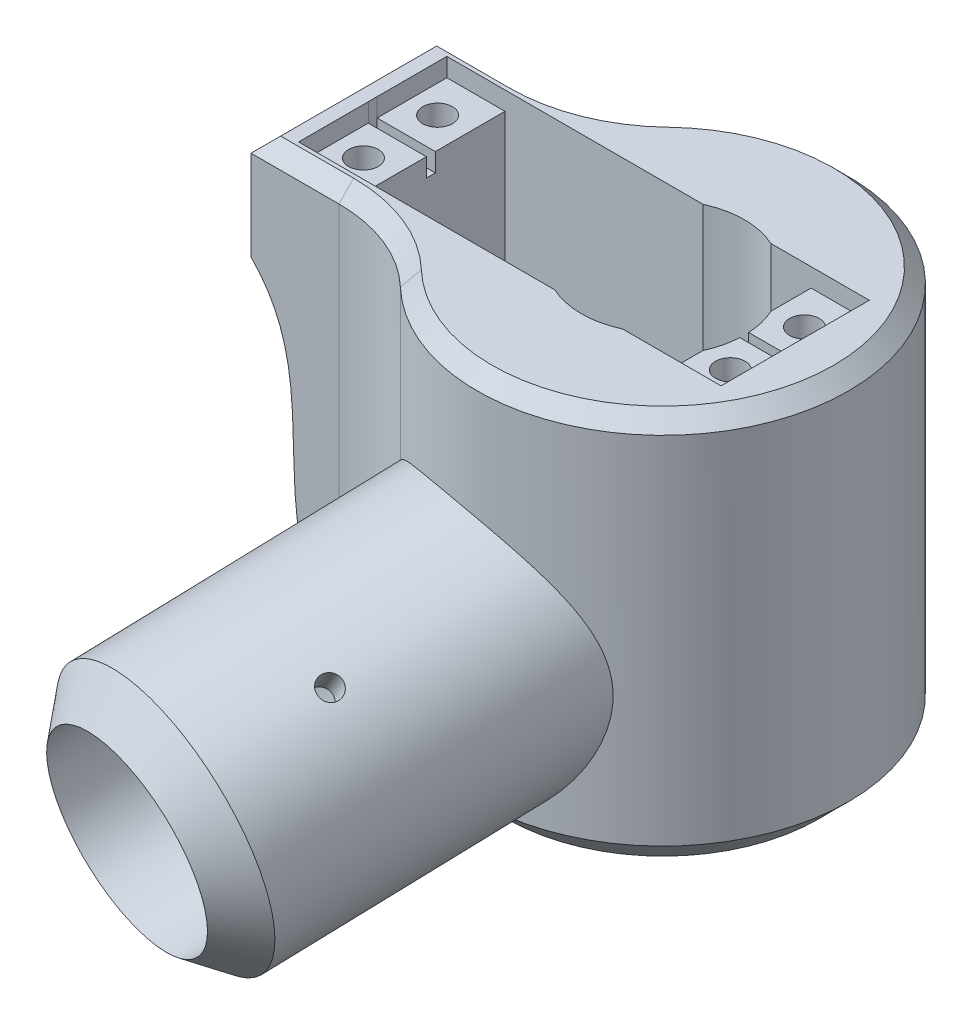
SolidWorks part; units mm, degrees
material "Melamine resin"
ref_plane "Front Plane" through (0, 0, 0) normal (0, 0, 1) x (1, 0, 0)
ref_plane "Top Plane" through (0, 0, 0) normal (0, 1, 0) x (1, 0, 0)
ref_plane "Right Plane" through (0, 0, 0) normal (1, 0, 0) x (0, 0, -1)
sketch "Sketch1" plane through (0, 0, 0) normal (0, 1, 0) x (1, 0, 0)
  line L3 (-34.0477, -12.5248) -> (-22.1886, -12.5248)
  line L4 (-34.0477, -12.5248) -> (-34.0477, 12.5248)
  line L5 (-34.0477, 12.5248) -> (-22.1886, 12.5248)
  arc A3 (-8.3278, -18.0914) -> (-22.1886, -12.5248) centre (-22.1886, -32.5646) ccw
  arc A4 (-22.1886, 12.5248) -> (-8.3278, 18.0914) centre (-22.1886, 32.5646) ccw
  arc A5 (-8.3278, -18.0914) -> (-8.3278, 18.0914) centre (8.9981, 0) ccw
  dimension "D1" = 20.0397
  dimension "D2" = 25.0497
extrude "Boss-Extrude2" add sketch "Sketch1" along normal blind 54
ref_axis "Axis1" through (8.9981, 54, 0) along (0, -1, 0)
ref_point "Point1"
sketch3d "3DSketch1"
  line L0 (8.9981, 25, 0) -> (-7.5398, 5.3755, 91.6321)
  line L4 (-23.4294, -13.4798, 179.6725) -> (8.9981, 25, 0) construction
ref_plane "Plane1" through (0, 25, 0) normal (0, 1, 0) x (1, 0, 0)
sketch "Sketch2" plane through (0, 25, 0) normal (0, 1, 0) x (1, 0, 0)
  point P0 (8.9981, 0)
chamfer "Chamfer1" distance 2 angle 45 5 edges at (-14.7202, 54, 13.9685) (-14.7202, 54, -13.9685) (34.0477, 54, 0) (-28.1181, 54, 12.5248) (-28.1181, 54, -12.5248)
ref_plane "Plane2" through (8.9981, 25, 0) normal (-0.1738, -0.2062, 0.9629) x (0.9848, -0.0364, 0.1699)
sketch "Sketch3" plane through (8.9981, 25, 0) normal (-0.1738, -0.2062, 0.9629) x (0.9848, -0.0364, 0.1699)
  circle A0 centre (0, 0) radius 17.5
  dimension "D1" = 35
extrude "Boss-Extrude3" add sketch "Sketch3" along a picked direction on the side of the normal blind 65
sketch "Sketch5" plane through (-10.1287, -12.0192, 56.1209) normal (-0.1738, -0.2062, 0.9629) x (0.9848, -0.0373, 0.1698)
  circle A0 centre (7.9298, 24.4526) radius 12.9
  dimension "D1" = 25.8
extrude "Cut-Extrude1" cut sketch "Sketch5" against normal blind 40
chamfer "Chamfer2" distance 6 angle 45 1 edges at (-2.2985, -5.5169, 58.9267)
ref_plane "Plane3" through (-22.1886, 52, -12.5248) normal (-0.5664, -0.779, -0.2691) x (-0.8242, 0.5354, 0.1848)
sketch "Sketch6" plane through (-22.1886, 52, -12.5248) normal (-0.5664, -0.779, -0.2691) x (-0.8242, 0.5354, 0.1848)
  line L0 (-26.8776, -71.5719) -> (-28.5511, -63.7489) construction
  line L2 (-37.8434, -20.6484) -> (-17.7885, -113.6691) construction
  circle A0 centre (-28.5511, -63.7489) radius 1.5
  dimension "D1" = 3
  dimension "D2" = 8
extrude "Cut-Extrude2" cut sketch "Sketch6" against normal mid plane 97
ref_point "Point2"
sketch "Sketch7" plane through (0, 0, 0) normal (0, -1, 0) x (-1, 0, 0)
  circle A0 centre (-8.9981, 0) radius 4
  dimension "D1" = 8
extrude "Cut-Extrude3" cut sketch "Sketch7" against normal blind 82
sketch "Sketch9" plane through (0, 0, 0) normal (0, -1, 0) x (1, 0, 0)
  circle A0 centre (8.9981, 0) radius 11
  dimension "D1" = 22
extrude "Cut-Extrude4" cut sketch "Sketch9" against normal blind 8
chamfer "Chamfer3" distance 2 angle 45 1 edges at (-34.0477, 54, 0)
sketch "Sketch10" plane through (0, 0, -12.5248) normal (0, 0, -1) x (-1, 0, 0)
  line L0 (22.1867, 0) -> (34.0477, 0)
  line L1 (34.0477, 0) -> (34.0477, 39.8592)
  line L2 (34.0477, 52) -> (34.0477, 0) construction
  line L3 (34.0477, 52) -> (22.1886, 52) construction
  spline S0 degree 3 poles (22.1867, 0) (33.5541, 11.2638) (23.1647, 28.9343) (34.0477, 39.8592) knots 0 0 0 0 1 1 1 1
extrude "Cut-Extrude5" cut sketch "Sketch10" against normal blind 96
sketch3d "3DSketch2"
  line L0 (8.9981, 54, 0) -> (8.9981, 0, 0) construction
  point P0 (8.9981, 25, 0)
sketch "Sketch11" plane through (0, 54, 0) normal (0, 1, 0) x (1, 0, 0)
  line L0 (25.8463, 0) -> (-43.2495, 0) construction
  line L1 (18.9981, 10.25) -> (-22.3055, 10.25)
  line L2 (18.9981, 10.25) -> (18.9981, -10.25)
  line L3 (18.9981, -10.25) -> (-22.3055, -10.25)
  line L4 (-22.3055, 10.25) -> (-22.3055, -10.25)
  line L5 (18.9981, 10.25) -> (-22.3055, -10.25) construction
  line L6 (18.9981, -10.25) -> (-22.3055, 10.25) construction
  line L7 (-29.1537, 10) -> (25.8463, 10)
  line L8 (-29.1537, 10) -> (-29.1537, -10)
  line L9 (-29.1537, -10) -> (25.8463, -10)
  line L10 (25.8463, 10) -> (25.8463, -10)
  line L11 (-29.1537, 10) -> (25.8463, -10) construction
  line L12 (-29.1537, -10) -> (25.8463, 10) construction
  line L13 (-1.6537, 0) -> (-1.6537, -13.0522) construction
  line L14 (12.1499, 0.6) -> (25.8463, 0.6)
  line L15 (12.1499, 0.6) -> (12.1499, -0.6)
  line L16 (12.1499, -0.6) -> (25.8463, -0.6)
  line L17 (25.8463, 0.6) -> (25.8463, -0.6)
  line L18 (12.1499, 0.6) -> (25.8463, -0.6) construction
  line L19 (12.1499, -0.6) -> (25.8463, 0.6) construction
  line L20 (-1.6537, -13.0522) -> (-1.6537, 13.6107) construction
  line L21 (-29.1537, 10) -> (-29.1537, -10)
  line L22 (-15.4573, 0.6) -> (-15.4573, -0.6)
  line L23 (-15.4573, -0.6) -> (-29.1537, -0.6)
  line L24 (-15.4573, 0.6) -> (-29.1537, 0.6)
  circle A0 centre (23.0963, -5) radius 2
  circle A1 centre (23.0963, 5) radius 2
  circle A2 centre (-26.4037, -5) radius 2
  circle A3 centre (-26.4037, 5) radius 2
  point P0 (7.4947, -4.5406)
  point P5 (-1.6537, 0)
  point P10 (18.9981, 0)
  circle M6 centre (8.9981, 0) radius 4
  dimension "D5" = 4
  dimension "D1" = 20.5
  dimension "D2" = 41.3036
  dimension "D3" = 55
  dimension "D4" = 1.2
  dimension "D6" = 5
  dimension "D7" = 2.75
  dimension "D8" = 10
extrude "Cut-Extrude6" cut sketch "Sketch11" against normal blind 34 contours L24 L22 L23 L4 L9 L2 L16 L14 L7 M6 | A1 | A0 | A2 | A3 | L16 L2 L14 M6 | L15 L16 L14 M6 | L16 L15 L14 M6 | L22 L24 L4 L23 region at (-2.3392, 54, 0) region at (15.9905, 54, 0) region at (-18.8814, 54, 0) region at (12.5665, 54, 0) region at (8.9256, 54, 0) region at (23.0963, 54, 5) region at (23.0963, 54, -5) region at (-26.4037, 54, 5) region at (-26.4037, 54, -5)
sketch "Sketch12" plane through (0, 54, 0) normal (0, 1, 0) x (1, 0, 0)
  line L0 (18.9981, 0) -> (-33.6264, 0) construction
  line L1 (18.9981, 10) -> (18.9981, -10) construction
  line L2 (0, 0) -> (0, -14.2019) construction
  line L3 (11.1481, 0.6) -> (26.8481, 0.6)
  line L4 (11.1481, 0.6) -> (11.1481, -0.6)
  line L5 (11.1481, -0.6) -> (26.8481, -0.6)
  line L6 (26.8481, 0.6) -> (26.8481, -0.6)
  line L7 (11.1481, 0.6) -> (26.8481, -0.6) construction
  line L8 (11.1481, -0.6) -> (26.8481, 0.6) construction
  line L9 (0, -14.2019) -> (0, 17.0976) construction
  line L10 (18.9981, 10) -> (18.9981, -10) construction
  line L11 (-22.3055, 10) -> (-22.3055, -10) construction
  line L12 (-14.4555, 0.6) -> (-30.1555, 0.6)
  line L13 (-14.4555, 0.6) -> (-14.4555, -0.6)
  line L14 (-14.4555, -0.6) -> (-30.1555, -0.6)
  line L15 (-30.1555, 0.6) -> (-30.1555, -0.6)
  line L16 (-14.4555, 0.6) -> (-30.1555, -0.6) construction
  line L17 (-14.4555, -0.6) -> (-30.1555, 0.6) construction
  point P14 (-22.3055, 0)
  dimension "D1" = 1.2
  dimension "D2" = 7.85
  dimension "D3" = 1.2
  dimension "D4" = 7.85
extrude "Cut-Extrude7" cut sketch "Sketch12" against normal blind 5
sketch "Sketch13" plane through (0, 54, 0) normal (0, 1, 0) x (1, 0, 0)
  line L0 (26.8481, -0.6) -> (26.8481, 0.6) construction
  line L1 (-30.1519, 10) -> (26.8481, 10)
  line L2 (-30.1519, 10) -> (-30.1519, -10)
  line L3 (-30.1519, -10) -> (26.8481, -10)
  line L4 (26.8481, 10) -> (26.8481, -10)
  line L5 (-30.1519, 10) -> (26.8481, -10) construction
  line L6 (-30.1519, -10) -> (26.8481, 10) construction
  line L7 (-1.6519, 0) -> (2.2395, 0) construction
  dimension "D1" = 20
  dimension "D2" = 57
extrude "Cut-Extrude8" cut sketch "Sketch13" against normal blind 2.5
sketch "Sketch14" plane through (0, 54, 0) normal (0, 1, 0) x (1, 0, 0)
  circle A0 centre (8.9981, 0) radius 11
  dimension "D1" = 22
extrude "Cut-Extrude9" cut sketch "Sketch14" against normal blind 42
chamfer "Chamfer4" distance 4 angle 45 3 edges at (-14.7193, 0, 13.9688) (-14.7193, 0, -13.9688) (34.0477, 0, 0)
